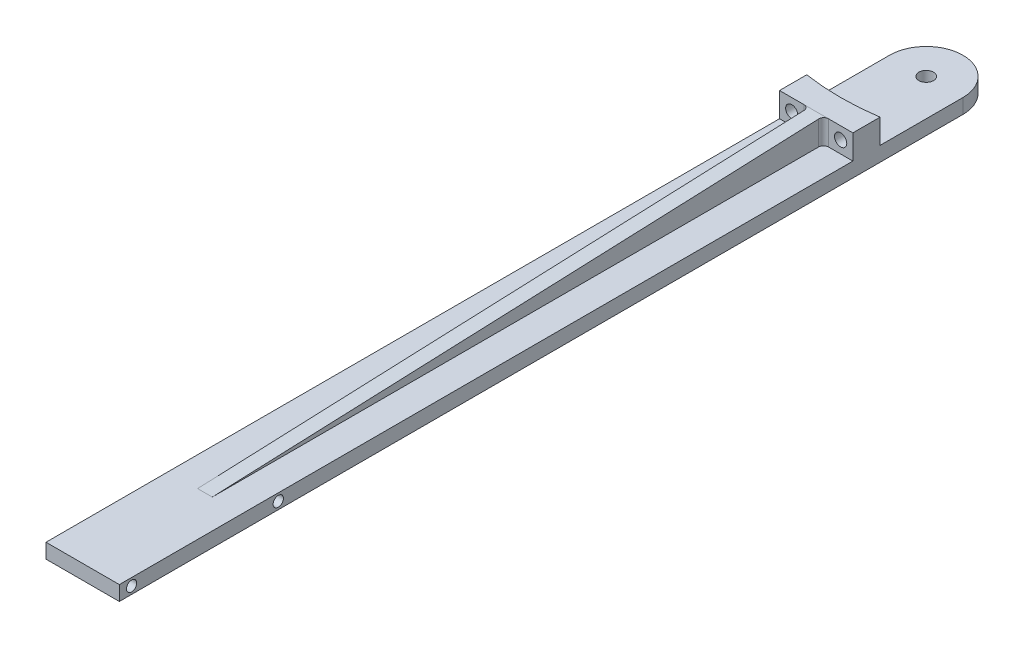
SolidWorks part; units mm, degrees
note: The reader was unsure of these and kept them because the rebuilt part matched: shared geometry of "Esquisse8<2>".
material "AISI 316 Barre d'acier inoxydable recuit (SS)"
ref_plane "Plan de face" through (0, 0, 0) normal (0, 0, 1) x (1, 0, 0)
ref_plane "Plan de dessus" through (0, 0, 0) normal (0, 1, 0) x (1, 0, 0)
ref_plane "Plan de droite" through (0, 0, 0) normal (1, 0, 0) x (0, 0, -1)
sketch "Esquisse1" plane through (0, 0, 0) normal (0, 0, 1) x (1, 0, 0)
  line L1 (0, 0) -> (30, 0)
  line L2 (0, 0) -> (0, 6)
  line L3 (0, 6) -> (30, 6)
  line L4 (30, 0) -> (30, 6)
  dimension "D1" = 30
  dimension "D2" = 6
extrude "Boss.-Extru.1" add sketch "Esquisse1" along normal blind 300
ref_plane "Plan1" through (15, 0, 0) normal (1, 0, 0) x (0, 0, -1)
sketch "Esquisse3" plane through (15, 0, 0) normal (1, 0, 0) x (0, 0, -1)
  line L0 (-250, 6) -> (0, 16)
  line L1 (-300, 6) -> (0, 6) construction
  line L2 (0, 16) -> (0, 6)
  line L3 (0, 6) -> (-250, 6)
  dimension "D1" = 10
  dimension "D2" = 250
extrude "Boss.-Extru.2" add sketch "Esquisse3" against normal blind 3 and the other way blind 3
sketch "Esquisse4" plane through (0, 0, 0) normal (0, 0, -1) x (-1, 0, 0)
  line L0 (-12, 16) -> (-18, 16) construction
  line L1 (-30, 0) -> (0, 0)
  line L2 (-30, 0) -> (-30, 16)
  line L3 (-30, 16) -> (0, 16)
  line L4 (0, 0) -> (0, 16)
  line L5 (-15, 16) -> (-15, 0) construction
  line L6 (-24, 16) -> (-24, 0) construction
  line L7 (0, 0) -> (-30, 0) construction
  dimension "D3" = 6
  dimension "D4" = 9
extrude "Boss.-Extru.3" add sketch "Esquisse4" along normal blind 10
sketch "Esquisse7" plane through (0, 0, 0) normal (0, -1, 0) x (1, 0, 0)
  line L0 (0, -10) -> (0, -45)
  line L1 (0, -45) -> (30, -45) construction
  line L2 (30, -45) -> (30, -10)
  line L3 (0, -10) -> (30, -10)
  line L4 (15, -10) -> (15, -48.1534) construction
  circle A1 centre (15, -45) radius 3
  arc A2 (0, -45) -> (30, -45) centre (15, -45) ccw
  point P13 (15, -45)
  dimension "D1" = 35
  dimension "D4" = 6
extrude "Boss.-Extru.5" add sketch "Esquisse7" against normal up to vertex (6 mm away)
sketch "Esquisse8" plane through (0, 0, 0) normal (-1, 0, 0) x (0, 0, 1)
  line L0 (300, 3) -> (40.4948, 3) construction
  line L1 (300, 6) -> (300, 0) construction
  circle A0 centre (295, 3) radius 2.1
  circle A1 centre (235, 3) radius 2.1
  dimension "D2" = 4.2
  dimension "D1" = 60
  dimension "D3" = 5
extrude "Enlèv. mat.-Extru.1" cut sketch "Esquisse8" against normal blind 12
extrude "Enlèv. mat.-Extru.3" cut sketch "Esquisse8<2>" along normal blind 12 from surface at -30 starting at face at (30, 7, 61.25)
sketch "Esquisse8<2>" plane through (0, 0, 0) normal (-1, 0, 0) x (0, 0, 1) same geometry as "Esquisse8"
sketch "Esquisse9" plane through (0, 16, 0) normal (0, 1, 0) x (1, 0, 0)
  line L0 (0, 11.1314) -> (0, 0)
  line L1 (0, 0) -> (30, 0)
  line L2 (30, 0) -> (30, 11.1314)
  line L3 (0, 10) -> (0, 45) construction
  line L4 (0, 10) -> (30, 10) construction
  line L5 (15, 45) -> (15, 10) construction
  arc A0 (0, 11.1314) -> (30, 11.1314) centre (15, 110) ccw
  dimension "D1" = 100
extrude "Boss.-Extru.6" add sketch "Esquisse9" against normal up to vertex (16 mm away)
sketch "Esquisse10" plane through (0, 0, 0) normal (0, 0, 1) x (1, 0, 0)
  line L0 (35, 11) -> (1, 11) construction
  line L3 (15, 16) -> (15, 6) construction
  line L4 (12, 16) -> (18, 16) construction
  line L5 (12, 6) -> (18, 6) construction
  line L6 (30, 6) -> (18, 6) construction
  circle A0 centre (5, 11) radius 2.5
  circle A1 centre (25, 11) radius 2.5
  point P16 (0, 0)
  point P17 (0, 0)
  dimension "D1" = 5
  dimension "D2" = 20
  dimension "D3" = 5
extrude "Enlèv. mat.-Extru.4" cut sketch "Esquisse10" against normal through all
fillet "Congé1" radius 2 2 edges at (12, 11, 0) (18, 11, 0)
